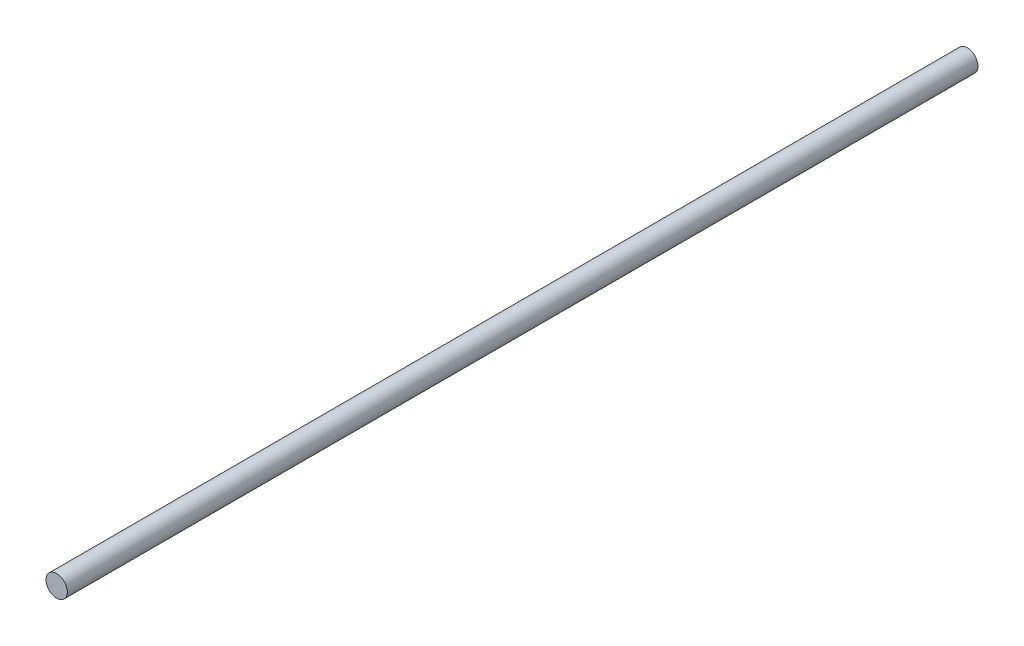
SolidWorks part; units mm, degrees
material "Cast Stainless Steel"
ref_plane "Front Plane" through (0, 0, 0) normal (0, 0, 1) x (1, 0, 0)
ref_plane "Top Plane" through (0, 0, 0) normal (0, 1, 0) x (1, 0, 0)
ref_plane "Right Plane" through (0, 0, 0) normal (1, 0, 0) x (0, 0, -1)
sketch "Sketch1" plane through (0, 0, 0) normal (0, 0, 1) x (1, 0, 0)
  circle A0 centre (0, 0) radius 9.525
extrude "Boss-Extrude1" add sketch "Sketch1" along normal blind 812.8
